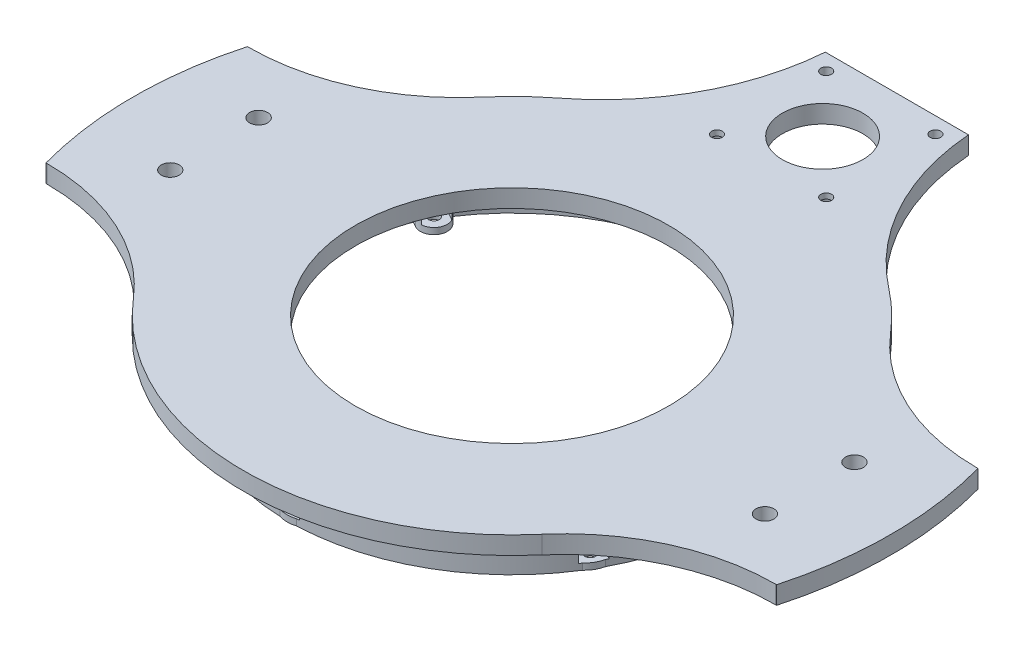
SolidWorks part; units mm, degrees
material "ABS"
ref_plane "Front Plane" through (0, 0, 0) normal (0, 0, 1) x (1, 0, 0)
ref_plane "Top Plane" through (0, 0, 0) normal (0, 1, 0) x (1, 0, 0)
ref_plane "Right Plane" through (0, 0, 0) normal (1, 0, 0) x (0, 0, -1)
sketch "Sketch1" plane through (0, 0, 0) normal (0, 1, 0) x (1, 0, 0)
  circle A0 centre (0, 0) radius 76.2
  circle A1 centre (0, 0) radius 44.45
  dimension "D1" = 152.4
  dimension "D2" = 88.9
extrude "Boss-Extrude1" add sketch "Sketch1" along normal blind 5.08
sketch "Sketch6" plane through (0, 5.08, 0) normal (0, 1, 0) x (1, 0, 0)
  line L1 (-103.6593, 28.575) -> (-70.6393, 28.575)
  line L2 (-103.6593, -28.575) -> (-70.6393, -28.575)
  line L3 (0, 0) -> (0, 24.6731) construction
  line L4 (103.6593, -28.575) -> (70.6393, -28.575)
  line L6 (103.6593, 28.575) -> (70.6393, 28.575)
  circle A0 centre (0, 0) radius 76.2 construction
  arc A1 (-70.6393, 28.575) -> (-70.6393, -28.575) centre (0, 0) ccw
  arc A2 (70.6393, -28.575) -> (70.6393, 28.575) centre (0, 0) ccw
  arc A3 (-103.6593, 28.575) -> (-103.6593, -28.575) centre (0, 0) ccw
  arc A4 (103.6593, -28.575) -> (103.6593, 28.575) centre (0, 0) ccw
  point P3 (-103.6593, 0)
  dimension "D1" = 33.02
  dimension "D2" = 57.15
  dimension "D3" = 33.02
extrude "Boss-Extrude12" add sketch "Sketch6" against normal through all
sketch "Sketch7" plane through (0, 5.08, 0) normal (0, 1, 0) x (1, 0, 0)
  line L0 (-103.6593, 28.575) -> (-103.3217, 28.575)
  line L1 (-103.6593, 28.575) -> (-103.6593, -28.575)
  line L2 (-103.6593, -28.575) -> (-103.3217, -28.575)
  line L4 (103.3217, -28.575) -> (103.6593, -28.575)
  line L5 (103.6593, -28.575) -> (103.6593, 28.575)
  line L6 (103.6593, 28.575) -> (103.3217, 28.575)
  arc A0 (-57.9374, -49.4944) -> (57.9374, -49.4944) centre (0, 0) ccw
  arc A1 (57.9374, 49.4944) -> (-57.9374, 49.4944) centre (0, 0) ccw
  arc A2 (103.3217, 28.575) -> (57.9374, 49.4944) centre (103.3217, 88.265) cw
  arc A3 (57.9374, -49.4944) -> (103.3217, -28.575) centre (103.3217, -88.265) cw
  arc A4 (-103.3217, -28.575) -> (-57.9374, -49.4944) centre (-103.3217, -88.265) cw
  arc A5 (-103.3217, 28.575) -> (-57.9374, 49.4944) centre (-103.3217, 88.265) ccw
  circle A6 centre (0, 0) radius 44.45
  point P20 (70.6393, 28.575)
  point P23 (70.6393, -28.575)
  point P26 (-70.6393, -28.575)
  point P29 (-70.6393, 28.575)
  dimension "D1" = 59.69
extrude "Boss-Extrude13" add sketch "Sketch7" against normal through all
sketch "Sketch8" plane through (0, 5.08, 0) normal (0, 1, 0) x (1, 0, 0)
  circle A1 centre (-84.6093, 12.7) radius 2.54
  circle A2 centre (-84.2717, -12.7) radius 2.54
  circle A3 centre (84.6093, 12.573) radius 2.54
  circle A4 centre (84.6093, -12.827) radius 2.54
  dimension "D2" = 15.875
  dimension "D3" = 25.4
  dimension "D4" = 19.05
  dimension "D5" = 5.08
  dimension "D6" = 5.08
  dimension "D7" = 5.08
  dimension ".20" = 5.08
  dimension "D8" = 25.4
  dimension "D9" = 16.002
  dimension "D10" = 19.05
  dimension "D1" = 19.05
extrude "Cut-Extrude1" cut sketch "Sketch8" against normal through all
sketch "Sketch11" plane through (0, 0, 0) normal (0, -1, 0) x (1, 0, 0)
  circle A0 centre (84.6093, -12.573) radius 2.5577
  circle A1 centre (84.6093, 12.827) radius 2.4439
  circle A2 centre (-84.2717, 12.7) radius 2.4457
  circle A3 centre (-84.6093, -12.7) radius 2.5634
extrude "Cut-Extrude2" cut sketch "Sketch11" against normal through all
sketch "Sketch12" plane through (0, 0, 0) normal (0, -1, 0) x (1, 0, 0)
  circle A0 centre (0, 0) radius 63.5
  circle A1 centre (0, 0) radius 62.23
  dimension "D1" = 127
  dimension "D2" = 124.46
extrude "Boss-Extrude15" add sketch "Sketch12" along normal blind 13.716
sketch "Sketch13" plane through (0, 0, 0) normal (0, -1, 0) x (1, 0, 0)
  circle A0 centre (0, 0) radius 63.5
  circle A1 centre (0, 0) radius 66.04
  dimension "D1" = 2.54
extrude "Boss-Extrude16" add sketch "Sketch13" along normal blind 3.81
sketch "Sketch14" plane through (0, 0, 0) normal (0, -1, 0) x (1, 0, 0)
  line L1 (20.32, -64.77) -> (-20.32, -64.77)
  line L2 (20.32, -64.77) -> (20.32, -109.22)
  line L3 (20.32, -109.22) -> (-20.32, -109.22)
  line L4 (-20.32, -64.77) -> (-20.32, -109.22)
  circle A2 centre (0, -88.138) radius 11.43
  dimension "D3" = 22.86
  dimension "D4" = 23.368
  dimension "D5" = 20.32
  dimension "D6" = 64.77
  dimension "D1" = 44.45
  dimension "D2" = 40.64
extrude "Boss-Extrude17" add sketch "Sketch14" against normal blind 5.08
sketch "Sketch15" plane through (0, 5.08, 0) normal (0, 1, 0) x (1, 0, 0)
  line L0 (-20.32, 109.22) -> (20.32, 109.22) construction
  line L1 (20.32, 109.22) -> (20.32, 73.4407) construction
  circle A0 centre (0, 88.138) radius 11.43
  circle A1 centre (-15.494, 104.648) radius 1.524
  circle A2 centre (15.494, 104.648) radius 1.524
  circle A3 centre (15.494, 73.66) radius 1.524
  circle A4 centre (-15.494, 73.66) radius 1.524
  dimension "D1" = 3.048
  dimension "D2" = 3.048
  dimension "D3" = 3.048
  dimension "D4" = 3.048
  dimension "D5" = 30.988
  dimension "D6" = 30.988
  dimension "D7" = 4.572
  dimension "D8" = 4.572
  dimension "D9" = 30.988
  dimension "D10" = 30.988
  dimension "D11" = 4.826
  dimension "D12" = 4.826
  dimension "D13" = 22.86
extrude "Cut-Extrude3" cut sketch "Sketch15" against normal blind 5.08
sketch "Sketch17" plane through (0, 0, 0) normal (0, -1, 0) x (1, 0, 0)
  arc A0 (53.7684, -33.7818) -> (56.1401, -29.6739) centre (0, 0) ccw
  arc A1 (2.3717, -63.4557) -> (-2.3717, -63.4557) centre (0, -55.88) cw
  arc A2 (-53.7684, -33.7818) -> (-56.1401, -29.6739) centre (-48.3935, -27.94) cw
  circle A3 centre (0, 0) radius 63.5 construction
  arc A4 (-56.1401, 29.6739) -> (-53.7684, 33.7818) centre (-48.3935, 27.94) cw
  arc A5 (-2.3717, 63.4557) -> (2.3717, 63.4557) centre (0, 55.88) cw
  arc A6 (53.7684, 33.7818) -> (56.1401, 29.6739) centre (48.3935, 27.94) cw
  arc A7 (56.1401, -29.6739) -> (53.7684, -33.7818) centre (48.3935, -27.94) cw
  arc A8 (-2.3717, -63.4557) -> (2.3717, -63.4557) centre (0, 0) ccw
  arc A9 (-56.1401, -29.6739) -> (-53.7684, -33.7818) centre (0, 0) ccw
  arc A10 (-53.7684, 33.7818) -> (-56.1401, 29.6739) centre (0, 0) ccw
  arc A11 (2.3717, 63.4557) -> (-2.3717, 63.4557) centre (0, 0) ccw
  arc A12 (56.1401, 29.6739) -> (53.7684, 33.7818) centre (0, 0) ccw
  point P26 (0, 0)
  dimension "D1" = 55.88
  dimension "D2" = 127
  dimension "D4" = 127
  dimension "D3" = 6
extrude "Boss-Extrude19" add sketch "Sketch17" along normal through all
sketch "Sketch18" plane through (0, 0, 0) normal (0, -1, 0) x (1, 0, 0)
  line L0 (-3.81, -60.579) -> (-3.81, -62.1133)
  line L1 (3.81, -60.579) -> (3.81, -62.1133)
  line L2 (-54.368, -26.9899) -> (-55.6967, -27.7571)
  line L3 (-50.558, -33.5891) -> (-51.8867, -34.3562)
  line L4 (-50.558, 33.5891) -> (-51.8867, 34.3562)
  line L5 (-54.368, 26.9899) -> (-55.6967, 27.7571)
  line L6 (3.81, 60.579) -> (3.81, 62.1133)
  line L7 (-3.81, 60.579) -> (-3.81, 62.1133)
  line L8 (54.368, 26.9899) -> (55.6967, 27.7571)
  line L9 (50.558, 33.5891) -> (51.8867, 34.3562)
  line L10 (50.558, -33.5891) -> (51.8867, -34.3562)
  line L11 (54.368, -26.9899) -> (55.6967, -27.7571)
  arc A1 (3.81, -60.579) -> (-3.81, -60.579) centre (0, -60.579) ccw
  circle A7 centre (0, -60.579) radius 1.524
  circle A15 centre (-52.463, -30.2895) radius 1.524
  arc A16 (-50.558, -33.5891) -> (-54.368, -26.9899) centre (-52.463, -30.2895) ccw
  circle A18 centre (-52.463, 30.2895) radius 1.524
  arc A19 (-54.368, 26.9899) -> (-50.558, 33.5891) centre (-52.463, 30.2895) ccw
  circle A21 centre (0, 60.579) radius 1.524
  arc A22 (-3.81, 60.579) -> (3.81, 60.579) centre (0, 60.579) ccw
  circle A24 centre (52.463, 30.2895) radius 1.524
  arc A25 (50.558, 33.5891) -> (54.368, 26.9899) centre (52.463, 30.2895) ccw
  circle A27 centre (52.463, -30.2895) radius 1.524
  arc A28 (54.368, -26.9899) -> (50.558, -33.5891) centre (52.463, -30.2895) ccw
  circle A29 centre (0, 0) radius 62.23 construction
  arc A30 (51.8867, -34.3562) -> (55.6967, -27.7571) centre (0, 0) ccw
  arc A31 (-3.81, -62.1133) -> (3.81, -62.1133) centre (0, 0) ccw
  arc A32 (-55.6967, -27.7571) -> (-51.8867, -34.3562) centre (0, 0) ccw
  arc A33 (55.6967, 27.7571) -> (51.8867, 34.3562) centre (0, 0) ccw
  arc A34 (-51.8867, 34.3562) -> (-55.6967, 27.7571) centre (0, 0) ccw
  arc A35 (3.81, 62.1133) -> (-3.81, 62.1133) centre (0, 0) ccw
  point P17 (0, 0)
  point P29 (0, 0)
  point P42 (0, 0)
  dimension "D2" = 7.62
  dimension "D3" = 3.048
  dimension "D4" = 60.579
other "Pen Sketch1" parameters "D2"=11.8597, "D3"=2.2491, "D5"=6, "D4"=124.46, "D1"=6
extrude "Boss-Extrude20" add sketch "Sketch18" along normal through all
ref_plane "Plane1" through (0, 0, -62.1133) normal (0, 0, 1) x (1, 0, 0)
sketch "Sketch19" plane through (0, 0, -62.1133) normal (0, 0, 1) x (1, 0, 0)
  line L0 (-3.81, -13.716) -> (3.81, -13.716) construction
  line L1 (3.175, -11.938) -> (-3.175, -11.938)
  line L2 (3.175, -11.938) -> (3.175, -9.144)
  line L3 (3.175, -9.144) -> (-3.175, -9.144)
  line L4 (-3.175, -11.938) -> (-3.175, -9.144)
  line L5 (3.81, -13.716) -> (3.81, 0) construction
  dimension "D1" = 2.794
  dimension "D2" = 6.35
  dimension "D3" = 1.778
  dimension "D4" = 0.635
extrude "Cut-Extrude4" cut sketch "Sketch19" along normal blind 15.24 and the other way blind 15.24
pattern_circular "CirPattern1" count 6 over 360 about axis through (0, 0, 0) along (0, 1, 0) of "Cut-Extrude4"
sketch "Sketch21" plane through (0, 0, 0) normal (0, -1, 0) x (1, 0, 0)
  circle A0 centre (15.494, -73.66) radius 3.048
  circle A1 centre (-15.494, -73.66) radius 3.048
  dimension "D1" = 6.096
  dimension "D2" = 6.096
extrude "Cut-Extrude6" cut sketch "Sketch21" against normal blind 3.556
fillet "Fillet2" radius 68.58 2 edges at (20.32, 2.54, -73.4407) (-20.32, 2.54, -73.4407)
